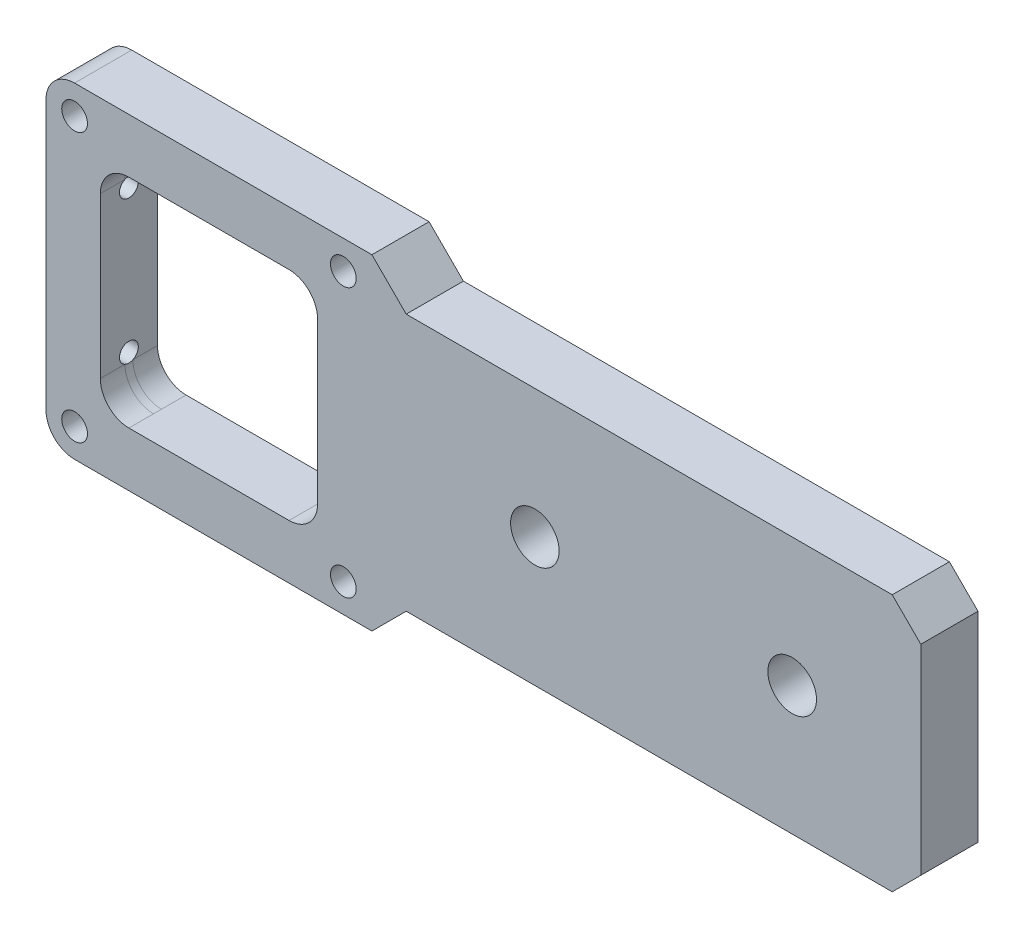
SolidWorks part; units mm, degrees
material "6061 合金"
ref_plane "前视基准面" through (0, 0, 0) normal (0, 0, 1) x (1, 0, 0)
ref_plane "上视基准面" through (0, 0, 0) normal (0, 1, 0) x (1, 0, 0)
ref_plane "右视基准面" through (0, 0, 0) normal (1, 0, 0) x (0, 0, -1)
sketch "草图1" plane through (0, 0, 0) normal (0, 0, 1) x (1, 0, 0)
  line L0 (28.5, -28.5) -> (34.5, -22.5)
  line L1 (-28.5, -28.5) -> (28.5, -28.5)
  line L2 (-28.5, -28.5) -> (-28.5, 28.5)
  line L3 (-28.5, 28.5) -> (28.5, 28.5)
  line L4 (28.5, -28.5) -> (28.5, 28.5)
  line L5 (-28.5, -28.5) -> (28.5, 28.5) construction
  line L6 (-28.5, 28.5) -> (28.5, -28.5) construction
  line L7 (124.5, -22.5) -> (28.5, -22.5)
  line L8 (124.5, -22.5) -> (124.5, 22.5)
  line L9 (124.5, 22.5) -> (28.5, 22.5)
  line L10 (28.5, -22.5) -> (28.5, 22.5)
  line L11 (124.5, -22.5) -> (28.5, 22.5) construction
  line L12 (124.5, 22.5) -> (28.5, -22.5) construction
  line L13 (124.5, 0) -> (-55.3636, 0) construction
  line L14 (28.5, 28.5) -> (34.5, 22.5)
  point P0 (0, 0)
  point P6 (76.5, 0)
  dimension "D1" = 63
  dimension "D2" = 57
  dimension "D3" = 45
  dimension "D4" = 90
  dimension "D5" = 45
extrude "凸台-拉伸1" add sketch "草图1" along normal mid plane 10 contours L1 L4 L3 L2 | L8 L9 L4 L7 | L9 L4 | L4 L7 region at (30.5, -24.5, 0) region at (0, 0, 0) region at (76.5, 0, 0) region at (30.5, 24.5, 0)
sketch "草图6" plane through (0, 0, 5) normal (0, 0, 1) x (1, 0, 0)
  circle A0 centre (0, 0) radius 10
  dimension "D1" = 20
extrude "过孔" cut sketch "草图6" against normal blind 10
sketch "草图19" plane through (0, 0, -5) normal (0, 0, -1) x (-1, 0, 0)
  circle A0 centre (0, 0) radius 12
  dimension "D1" = 24
extrude "轴承孔" cut sketch "草图19" against normal blind 5
hole_wizard "Ø8.5 (8.5) 直径孔1" positions "草图5" profile "草图4" hole size "Ø8.5" standard "GB" end condition through all
sketch "草图5" plane through (0, 0, 5) normal (0, 0, 1) x (1, 0, 0)
  line L1 (79.5, -22.5) -> (79.5, 22.5) construction
  line L2 (124.5, -22.5) -> (34.5, -22.5) construction
  line L3 (124.5, 22.5) -> (34.5, 22.5) construction
  line L5 (0, 0) -> (120.0042, 0) construction
  point P0 (57, 0)
  point P3 (102, 0)
  dimension "D1" = 45
sketch "草图4" plane through (57, 0, 5) normal (1, 0, 0) x (0, -1, 0)
  line L0 (0, 0) -> (0, 10)
  line L1 (0, 10) -> (4.25, 10)
  line L2 (4.25, 10) -> (4.25, 0)
  line L5 (4.25, 0) -> (0, 0)
  line L11 (0, -6.35) -> (0, 107.95) construction
  dimension "通孔孔直径" = 8.5
  dimension "通孔孔深度" = 10
hole_wizard "打孔尺寸(%根据)内六角圆柱头螺钉的类型1" positions "草图12" profile "草图11" counterbore size "M4" standard "GB" end condition through all
sketch "草图12" plane through (0, 0, -5) normal (0, 0, -1) x (-1, 0, 0)
  line L0 (0, 0) -> (0, -49.1013) construction
  line L2 (0, 0) -> (52.852, 0) construction
  point P0 (-23.5, 23.5)
  point P3 (23.5, 23.5)
  point P6 (23.5, -23.5)
  point P9 (-23.5, -23.5)
  dimension "D1" = 47
  dimension "D2" = 47
sketch "草图11" plane through (23.5, 23.5, -5) normal (1, 0, 0) x (0, 1, 0)
  line L0 (0, 0) -> (0, 10)
  line L1 (0, 10) -> (2.25, 10)
  line L3 (2.25, 10) -> (2.25, 4.6)
  line L4 (2.25, 4.6) -> (4, 4.6)
  line L5 (4, 4.6) -> (4, 0)
  line L7 (4, 0) -> (0, 0)
  line L11 (0, -6.35) -> (0, 107.95) construction
  dimension "通孔孔直径" = 4.5
  dimension "通孔孔深度" = 10
  dimension "柱形沉头孔直径" = 8
  dimension "柱形沉头孔深度" = 4.6
fillet "圆角1" radius 5 2 edges at (-28.5, 28.5, 0) (-28.5, -28.5, 0)
chamfer "倒角1" distance 5 angle 45 2 edges at (124.5, 22.5, 0) (124.5, -22.5, 0)
chamfer "倒角2" distance 0.2 angle 45 1 edges at (-12, 0, -5)
hole_wizard "M4 螺纹孔1" positions "草图21" profile "草图20" tap size "M4" standard "GB"
sketch "草图21" plane through (-28.5, 0, 0) normal (-1, 0, 0) x (0, 0, 1)
  line L0 (0, 0) -> (17.4295, 0) construction
  line L2 (0, 28.5) -> (0, -28.5) construction
  line L3 (-5, 28.5) -> (5, 28.5) construction
  line L4 (5, -28.5) -> (-5, -28.5) construction
  point P0 (0, 12.5)
  point P2 (0, -12.5)
  dimension "D1" = 25
sketch "草图20" plane through (-28.5, 12.5, 0) normal (0, 1, 0) x (0, 0, 1)
  line L0 (0, 0) -> (0, 15.5)
  line L1 (0, 15.5) -> (1.65, 15.5)
  line L2 (1.65, 15.5) -> (1.65, 0.2165)
  line L3 (1.65, 0.2165) -> (2.025, 0)
  line L5 (2.025, 0) -> (0, 0)
  line L6 (-1.65, 0.2165) -> (-2.025, 0) construction
  line L10 (0, 15.5) -> (-1.65, 15.5) construction
  line L11 (0, -6.35) -> (0, 107.95) construction
  dimension "螺纹孔钻头直径" = 3.3
  dimension "螺纹孔钻头深度" = 15.5
  dimension "近端锥形沉头孔直径" = 4.05
  dimension "近端锥形沉头孔角度" = 120
  dimension "导头角度" = 180
cosmetic thread "孔螺蚊线1" parameters "D1"=12, "D2"=4
cosmetic thread "孔螺蚊线2" parameters "D1"=12, "D2"=4
sketch "草图22" plane through (0, 0, -5) normal (0, 0, -1) x (-1, 0, 0)
  line L1 (-19, -19) -> (19, -19)
  line L2 (-19, -19) -> (-19, 19)
  line L3 (-19, 19) -> (19, 19)
  line L4 (19, -19) -> (19, 19)
  line L5 (-19, -19) -> (19, 19) construction
  line L6 (-19, 19) -> (19, -19) construction
  point P0 (0, 0)
  dimension "D1" = 38
  dimension "D2" = 38
extrude "切除-拉伸1" cut sketch "草图22" against normal blind 10
fillet "圆角2" radius 5 4 edges at (19, -19, 0) (-19, -19, 0) (-19, 19, 0) (19, 19, 0)
